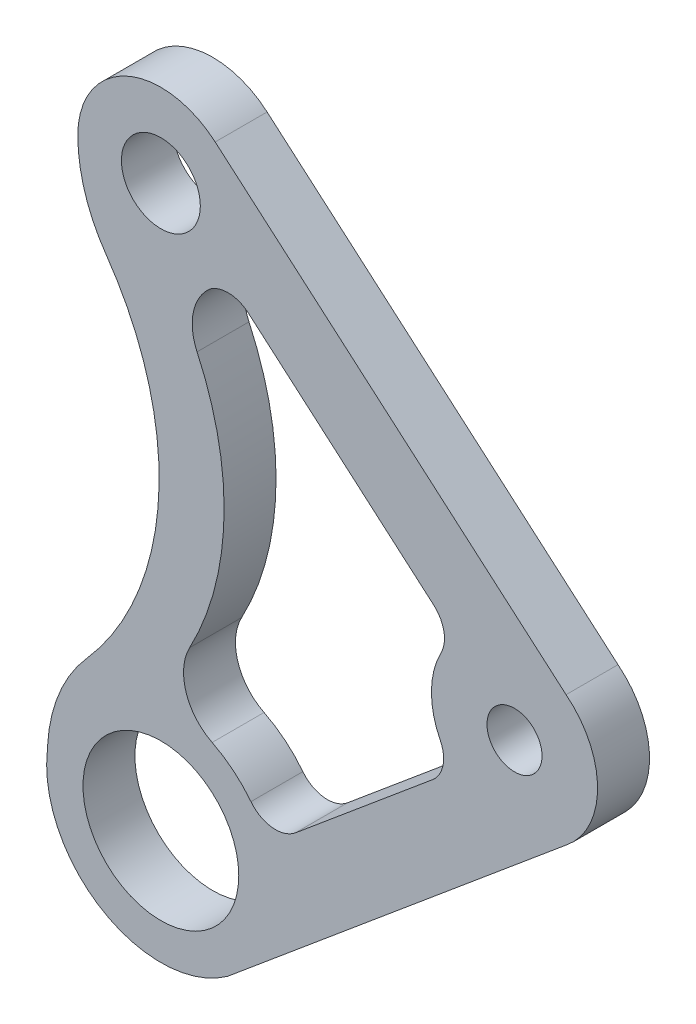
SolidWorks part; units mm, degrees
material "6061-T6 (SS)"
ref_plane "X-Y Datum" through (0, 0, 0) normal (0, 0, 1) x (1, 0, 0)
ref_plane "X-Z Datum" through (0, 0, 0) normal (0, 1, 0) x (1, 0, 0)
ref_plane "Y-Z Datum" through (0, 0, 0) normal (1, 0, 0) x (0, 0, -1)
sketch "Sketch1" plane through (0, 0, 0) normal (0, 0, 1) x (1, 0, 0)
  line L0 (0, 0) -> (0, 68.58) construction
  line L1 (0, 68.58) -> (43.2483, 31.2208) construction
  line L2 (43.2483, 31.2208) -> (0, 0) construction
  line L3 (-13.97, 0) -> (-10.16, 68.58)
  line L4 (6.6414, 76.2688) -> (49.5557, 39.1859)
  line L5 (49.5557, 23.2558) -> (8.1778, -11.3263)
  circle A0 centre (0, 0) radius 9.525
  circle A1 centre (43.2483, 31.2208) radius 3.3655
  circle A2 centre (0, 68.58) radius 4.826
  arc A3 (-10.16, 68.58) -> (6.6414, 76.2688) centre (0, 68.58) cw
  arc A4 (49.5557, 39.1859) -> (49.5557, 23.2558) centre (43.2483, 31.2208) cw
  arc A5 (8.1778, -11.3263) -> (-13.97, 0) centre (0, 0) cw
  point P12 (0, 0)
  point P14 (0, 0)
  point P15 (0, 0)
  point P16 (53.4083, 31.2208)
  dimension "D4" = 19.05
  dimension "D5" = 6.731
  dimension "D6" = 9.652
  dimension "D7" = 13.97
  dimension "D8" = 10.16
  dimension "D9" = 10.16
  dimension "D1" = 68.58
  dimension "D2" = 57.15
  dimension "D3" = 53.34
  dimension "D10" = 130.82
  dimension "D11" = 125.83
  dimension "D12" = 103.25
extrude "Boss-Extrude1" add sketch "Sketch1" along normal blind 6.35
sketch "Sketch2" plane through (0, 0, 6.35) normal (0, 0, 1) x (1, 0, 0)
  line L0 (-10.16, 68.58) -> (-13.97, 0) construction
  line L1 (-10.5128, 62.23) -> (-13.4408, 9.525)
  arc A0 (-10.5128, 62.23) -> (-13.4408, 9.525) centre (-35.7711, 37.1994) cw
  dimension "D3" = 35.56
  dimension "D1" = 6.35
  dimension "D2" = 9.525
extrude "Cut-Extrude1" cut sketch "Sketch2" against normal blind 6.35
fillet "Fillet1" radius 19.05 2 edges at (-10.5128, 62.23, 3.175) (-13.4408, 9.525, 3.175)
sketch "Sketch3" plane through (0, 0, 6.35) normal (0, 0, 1) x (1, 0, 0)
  line L2 (8.0877, 62.4306) -> (35.9845, 38.3245)
  line L3 (49.5557, 39.1859) -> (6.6414, 76.2688) construction
  line L6 (12.9992, 5.1168) -> (35.8725, 24.2335)
  arc A0 (35.9845, 38.3245) -> (35.8725, 24.2335) centre (43.2483, 31.2208) ccw
  arc A1 (-1.655, 13.8716) -> (12.9992, 5.1168) centre (0, 0) cw
  arc A3 (1.2017, 58.4913) -> (-1.655, 13.8716) centre (-27.8241, 37.9483) cw
  arc A6 (1.2017, 58.4913) -> (8.0877, 62.4306) centre (0, 68.58) ccw
  point P9 (0, 0)
  point P10 (0, 0)
  point P13 (0, 0)
  point P17 (0, 0)
  dimension "D1" = 10.16
  dimension "D2" = 10.16
  dimension "D3" = 13.97
  dimension "D6" = 6.7275
  dimension "D7" = 35.56
  dimension "D4" = 29.81
  dimension "D5" = 9.525
  dimension "D11" = 75.318
extrude "Cut-Extrude2" cut sketch "Sketch3" against normal blind 6.35
sketch3d "3DSketch1"
  line L0 (0, 68.58, 6.35) -> (0, 68.58, 0) construction
  line L1 (43.2483, 31.2208, 6.35) -> (43.2483, 31.2208, 0) construction
  point P0 (0, 68.58, 6.35)
  point P1 (43.2483, 31.2208, 6.35)
fillet "Fillet2" radius 3.81 4 edges at (35.9845, 38.3245, 3.175) (12.9992, 5.1168, 3.175) (35.8725, 24.2335, 3.175) (8.0877, 62.4306, 3.175)
fillet "Fillet4" radius 6.35 2 edges at (1.2017, 58.4913, 3.175) (-1.655, 13.8716, 3.175)
